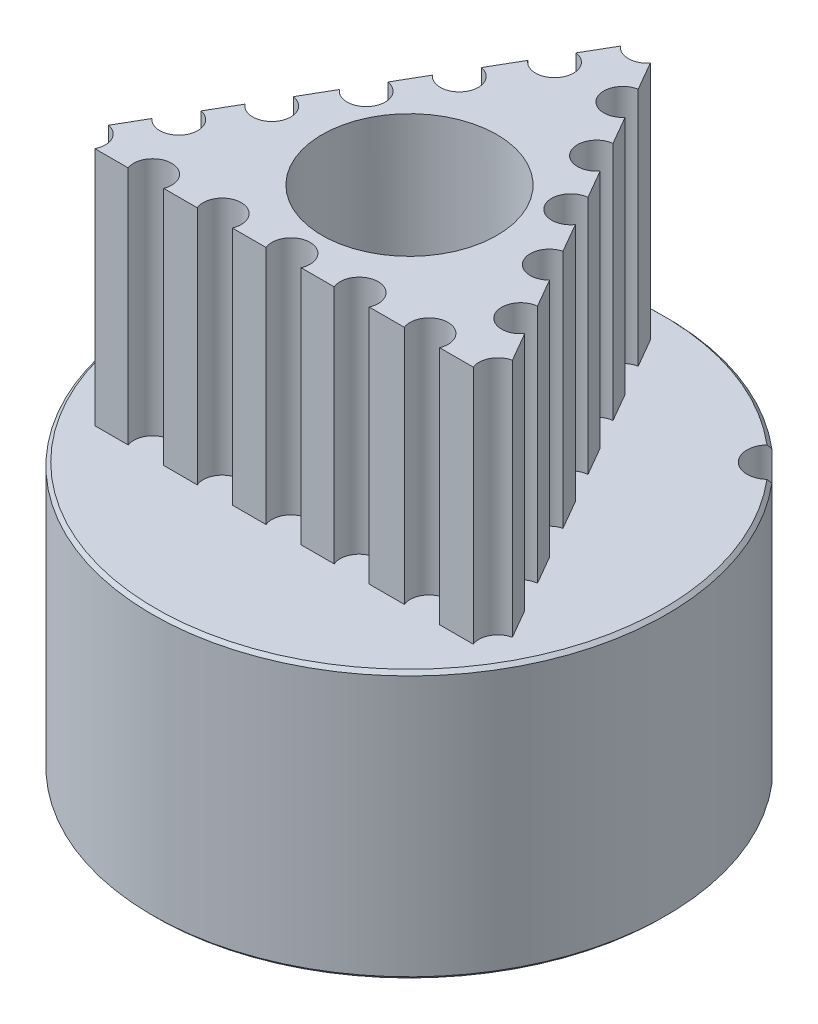
SolidWorks part; units mm, degrees
material "6061 slitina"
ref_plane "Přední rovina" through (0, 0, 0) normal (0, 0, 1) x (1, 0, 0)
ref_plane "Horní rovina" through (0, 0, 0) normal (0, 1, 0) x (1, 0, 0)
ref_plane "Pravá rovina" through (0, 0, 0) normal (1, 0, 0) x (0, 0, -1)
sketch "Skica1" plane through (0, 0, 0) normal (0, 1, 0) x (1, 0, 0)
  circle A0 centre (0, 0) radius 2.5
  arc B0 (-5.7301, 1.0983) -> (-5.3872, 2.2403) centre (-5.6803, 1.7058) ccw
  arc B1 (-5.7301, 1.0983) -> (-5.922, 1.0859) centre (-5.7841, 0.4401) ccw
  arc B2 (-5.922, 1.0859) -> (-6.0197, 1.0387) centre (-5.8743, 0.8624) ccw
  arc B3 (-6.0197, 1.0387) -> (-6.0791, 0.6004) centre (0, 0) ccw
  arc B4 (-6.0791, 0.6004) -> (-5.9974, 0.5289) centre (-5.892, 0.7317) ccw
  arc B5 (-5.9974, 0.5289) -> (-5.8158, 0.466) centre (-5.6927, 1.1148) ccw
  arc B6 (-5.7891, -0.7262) -> (-5.8158, 0.466) centre (-5.9294, -0.133) ccw
  arc B7 (-5.7891, -0.7262) -> (-5.9677, -0.7972) centre (-5.637, -1.3689) ccw
  arc B8 (-5.9677, -0.7972) -> (-6.0461, -0.8723) centre (-5.8532, -0.9951) ccw
  arc B9 (-6.0461, -0.8723) -> (-5.9671, -1.3075) centre (0, 0) ccw
  arc B10 (-5.9671, -1.3075) -> (-5.8673, -1.3503) centre (-5.8297, -1.1248) ccw
  arc B11 (-5.8673, -1.3503) -> (-5.6751, -1.354) centre (-5.7586, -0.6989) ccw
  arc B12 (-5.2813, -2.4796) -> (-5.6751, -1.354) centre (-5.5981, -1.9587) ccw
  arc B13 (-5.2813, -2.4796) -> (-5.4293, -2.6023) centre (-4.9381, -3.0438) ccw
  arc B14 (-5.4293, -2.6023) -> (-5.4806, -2.698) centre (-5.2593, -2.7551) ccw
  arc B15 (-5.4806, -2.698) -> (-5.271, -3.0875) centre (0, 0) ccw
  arc B16 (-5.271, -3.0875) -> (-5.1629, -3.0973) centre (-5.1968, -2.8713) ccw
  arc B17 (-5.1629, -3.0973) -> (-4.979, -3.0415) centre (-5.2608, -2.4442) ccw
  arc B18 (-4.2566, -3.9902) -> (-4.979, -3.0415) centre (-4.7188, -3.5928) ccw
  arc B19 (-4.2566, -3.9902) -> (-4.3594, -4.1527) centre (-3.7559, -4.4208) ccw
  arc B20 (-4.3594, -4.1527) -> (-4.3786, -4.2595) centre (-4.1505, -4.2455) ccw
  arc B21 (-4.3786, -4.2595) -> (-4.059, -4.5652) centre (0, 0) ccw
  arc B22 (-4.059, -4.5652) -> (-3.9531, -4.5412) centre (-4.0552, -4.3366) ccw
  arc B23 (-3.9531, -4.5412) -> (-3.7954, -4.4312) centre (-4.248, -3.9503) ccw
  arc B24 (-2.8152, -5.1103) -> (-3.7954, -4.4312) centre (-3.3776, -4.8751) ccw
  arc B25 (-2.8152, -5.1103) -> (-2.8628, -5.2965) centre (-2.2059, -5.3651) ccw
  arc B26 (-2.8628, -5.2965) -> (-2.8481, -5.4041) centre (-2.6354, -5.3203) ccw
  arc B27 (-2.8481, -5.4041) -> (-2.4496, -5.596) centre (0, 0) ccw
  arc B28 (-2.4496, -5.596) -> (-2.3563, -5.5405) centre (-2.5166, -5.3775) ccw
  arc B29 (-2.3563, -5.5405) -> (-2.2403, -5.3872) centre (-2.8194, -5.0696) ccw
  arc B30 (-1.0983, -5.7301) -> (-2.2403, -5.3872) centre (-1.7058, -5.6803) ccw
  arc B31 (-1.0983, -5.7301) -> (-1.0859, -5.922) centre (-0.4401, -5.7841) ccw
  arc B32 (-1.0859, -5.922) -> (-1.0387, -6.0197) centre (-0.8624, -5.8743) ccw
  arc B33 (-1.0387, -6.0197) -> (-0.6004, -6.0791) centre (0, 0) ccw
  arc B34 (-0.6004, -6.0791) -> (-0.5289, -5.9974) centre (-0.7317, -5.892) ccw
  arc B35 (-0.5289, -5.9974) -> (-0.466, -5.8158) centre (-1.1148, -5.6927) ccw
  arc B36 (0.7262, -5.7891) -> (-0.466, -5.8158) centre (0.133, -5.9294) ccw
  arc B37 (0.7262, -5.7891) -> (0.7972, -5.9677) centre (1.3689, -5.637) ccw
  arc B38 (0.7972, -5.9677) -> (0.8723, -6.0461) centre (0.9951, -5.8532) ccw
  arc B39 (0.8723, -6.0461) -> (1.3075, -5.9671) centre (0, 0) ccw
  arc B40 (1.3075, -5.9671) -> (1.3503, -5.8673) centre (1.1248, -5.8297) ccw
  arc B41 (1.3503, -5.8673) -> (1.354, -5.6751) centre (0.6989, -5.7586) ccw
  arc B42 (2.4796, -5.2813) -> (1.354, -5.6751) centre (1.9587, -5.5981) ccw
  arc B43 (2.4796, -5.2813) -> (2.6023, -5.4293) centre (3.0438, -4.9381) ccw
  arc B44 (2.6023, -5.4293) -> (2.698, -5.4806) centre (2.7551, -5.2593) ccw
  arc B45 (2.698, -5.4806) -> (3.0875, -5.271) centre (0, 0) ccw
  arc B46 (3.0875, -5.271) -> (3.0973, -5.1629) centre (2.8713, -5.1968) ccw
  arc B47 (3.0973, -5.1629) -> (3.0415, -4.979) centre (2.4442, -5.2608) ccw
  arc B48 (3.9902, -4.2566) -> (3.0415, -4.979) centre (3.5928, -4.7188) ccw
  arc B49 (3.9902, -4.2566) -> (4.1527, -4.3594) centre (4.4208, -3.7559) ccw
  arc B50 (4.1527, -4.3594) -> (4.2595, -4.3786) centre (4.2455, -4.1505) ccw
  arc B51 (4.2595, -4.3786) -> (4.5652, -4.059) centre (0, 0) ccw
  arc B52 (4.5652, -4.059) -> (4.5412, -3.9531) centre (4.3366, -4.0552) ccw
  arc B53 (4.5412, -3.9531) -> (4.4312, -3.7954) centre (3.9503, -4.248) ccw
  arc B54 (5.1103, -2.8152) -> (4.4312, -3.7954) centre (4.8751, -3.3776) ccw
  arc B55 (5.1103, -2.8152) -> (5.2965, -2.8628) centre (5.3651, -2.2059) ccw
  arc B56 (5.2965, -2.8628) -> (5.4041, -2.8481) centre (5.3203, -2.6354) ccw
  arc B57 (5.4041, -2.8481) -> (5.596, -2.4496) centre (0, 0) ccw
  arc B58 (5.596, -2.4496) -> (5.5405, -2.3563) centre (5.3775, -2.5166) ccw
  arc B59 (5.5405, -2.3563) -> (5.3872, -2.2403) centre (5.0696, -2.8194) ccw
  arc B60 (5.7301, -1.0983) -> (5.3872, -2.2403) centre (5.6803, -1.7058) ccw
  arc B61 (5.7301, -1.0983) -> (5.922, -1.0859) centre (5.7841, -0.4401) ccw
  arc B62 (5.922, -1.0859) -> (6.0197, -1.0387) centre (5.8743, -0.8624) ccw
  arc B63 (6.0197, -1.0387) -> (6.0791, -0.6004) centre (0, 0) ccw
  arc B64 (6.0791, -0.6004) -> (5.9974, -0.5289) centre (5.892, -0.7317) ccw
  arc B65 (5.9974, -0.5289) -> (5.8158, -0.466) centre (5.6927, -1.1148) ccw
  arc B66 (5.7891, 0.7262) -> (5.8158, -0.466) centre (5.9294, 0.133) ccw
  arc B67 (5.7891, 0.7262) -> (5.9677, 0.7972) centre (5.637, 1.3689) ccw
  arc B68 (5.9677, 0.7972) -> (6.0461, 0.8723) centre (5.8532, 0.9951) ccw
  arc B69 (6.0461, 0.8723) -> (5.9671, 1.3075) centre (0, 0) ccw
  arc B70 (5.9671, 1.3075) -> (5.8673, 1.3503) centre (5.8297, 1.1248) ccw
  arc B71 (5.8673, 1.3503) -> (5.6751, 1.354) centre (5.7586, 0.6989) ccw
  arc B72 (5.2813, 2.4796) -> (5.6751, 1.354) centre (5.5981, 1.9587) ccw
  arc B73 (5.2813, 2.4796) -> (5.4293, 2.6023) centre (4.9381, 3.0438) ccw
  arc B74 (5.4293, 2.6023) -> (5.4806, 2.698) centre (5.2593, 2.7551) ccw
  arc B75 (5.4806, 2.698) -> (5.271, 3.0875) centre (0, 0) ccw
  arc B76 (5.271, 3.0875) -> (5.1629, 3.0973) centre (5.1968, 2.8713) ccw
  arc B77 (5.1629, 3.0973) -> (4.979, 3.0415) centre (5.2608, 2.4442) ccw
  arc B78 (4.2566, 3.9902) -> (4.979, 3.0415) centre (4.7188, 3.5928) ccw
  arc B79 (4.2566, 3.9902) -> (4.3594, 4.1527) centre (3.7559, 4.4208) ccw
  arc B80 (4.3594, 4.1527) -> (4.3786, 4.2595) centre (4.1505, 4.2455) ccw
  arc B81 (4.3786, 4.2595) -> (4.059, 4.5652) centre (0, 0) ccw
  arc B82 (4.059, 4.5652) -> (3.9531, 4.5412) centre (4.0552, 4.3366) ccw
  arc B83 (3.9531, 4.5412) -> (3.7954, 4.4312) centre (4.248, 3.9503) ccw
  arc B84 (2.8152, 5.1103) -> (3.7954, 4.4312) centre (3.3776, 4.8751) ccw
  arc B85 (2.8152, 5.1103) -> (2.8628, 5.2965) centre (2.2059, 5.3651) ccw
  arc B86 (2.8628, 5.2965) -> (2.8481, 5.4041) centre (2.6354, 5.3203) ccw
  arc B87 (2.8481, 5.4041) -> (2.4496, 5.596) centre (0, 0) ccw
  arc B88 (2.4496, 5.596) -> (2.3563, 5.5405) centre (2.5166, 5.3775) ccw
  arc B89 (2.3563, 5.5405) -> (2.2403, 5.3872) centre (2.8194, 5.0696) ccw
  arc B90 (1.0983, 5.7301) -> (2.2403, 5.3872) centre (1.7058, 5.6803) ccw
  arc B91 (1.0983, 5.7301) -> (1.0859, 5.922) centre (0.4401, 5.7841) ccw
  arc B92 (1.0859, 5.922) -> (1.0387, 6.0197) centre (0.8624, 5.8743) ccw
  arc B93 (1.0387, 6.0197) -> (0.6004, 6.0791) centre (0, 0) ccw
  arc B94 (0.6004, 6.0791) -> (0.5289, 5.9974) centre (0.7317, 5.892) ccw
  arc B95 (0.5289, 5.9974) -> (0.466, 5.8158) centre (1.1148, 5.6927) ccw
  arc B96 (-0.7262, 5.7891) -> (0.466, 5.8158) centre (-0.133, 5.9294) ccw
  arc B97 (-0.7262, 5.7891) -> (-0.7972, 5.9677) centre (-1.3689, 5.637) ccw
  arc B98 (-0.7972, 5.9677) -> (-0.8723, 6.0461) centre (-0.9951, 5.8532) ccw
  arc B99 (-0.8723, 6.0461) -> (-1.3075, 5.9671) centre (0, 0) ccw
  arc B100 (-1.3075, 5.9671) -> (-1.3503, 5.8673) centre (-1.1248, 5.8297) ccw
  arc B101 (-1.3503, 5.8673) -> (-1.354, 5.6751) centre (-0.6989, 5.7586) ccw
  arc B102 (-2.4796, 5.2813) -> (-1.354, 5.6751) centre (-1.9587, 5.5981) ccw
  arc B103 (-2.4796, 5.2813) -> (-2.6023, 5.4293) centre (-3.0438, 4.9381) ccw
  arc B104 (-2.6023, 5.4293) -> (-2.698, 5.4806) centre (-2.7551, 5.2593) ccw
  arc B105 (-2.698, 5.4806) -> (-3.0875, 5.271) centre (0, 0) ccw
  arc B106 (-3.0875, 5.271) -> (-3.0973, 5.1629) centre (-2.8713, 5.1968) ccw
  arc B107 (-3.0973, 5.1629) -> (-3.0415, 4.979) centre (-2.4442, 5.2608) ccw
  arc B108 (-3.9902, 4.2566) -> (-3.0415, 4.979) centre (-3.5928, 4.7188) ccw
  arc B109 (-3.9902, 4.2566) -> (-4.1527, 4.3594) centre (-4.4208, 3.7559) ccw
  arc B110 (-4.1527, 4.3594) -> (-4.2595, 4.3786) centre (-4.2455, 4.1505) ccw
  arc B111 (-4.2595, 4.3786) -> (-4.5652, 4.059) centre (0, 0) ccw
  arc B112 (-4.5652, 4.059) -> (-4.5412, 3.9531) centre (-4.3366, 4.0552) ccw
  arc B113 (-4.5412, 3.9531) -> (-4.4312, 3.7954) centre (-3.9503, 4.248) ccw
  arc B114 (-5.1103, 2.8152) -> (-4.4312, 3.7954) centre (-4.8751, 3.3776) ccw
  arc B115 (-5.1103, 2.8152) -> (-5.2965, 2.8628) centre (-5.3651, 2.2059) ccw
  arc B116 (-5.2965, 2.8628) -> (-5.4041, 2.8481) centre (-5.3203, 2.6354) ccw
  arc B117 (-5.4041, 2.8481) -> (-5.596, 2.4496) centre (0, 0) ccw
  arc B118 (-5.596, 2.4496) -> (-5.5405, 2.3563) centre (-5.3775, 2.5166) ccw
  arc B119 (-5.5405, 2.3563) -> (-5.3872, 2.2403) centre (-5.0696, 2.8194) ccw
  dimension "D1" = 5
sketch_block_instance "Blok1-1"
sketch_block "Blok1"
extrude "Přidat vysunutím1" add sketch "Skica1" along normal blind 7 from offset 7.8
sketch "Skica2" plane through (0, 7.8, 0) normal (0, -1, 0) x (1, 0, 0)
  circle A0 centre (0, 0) radius 3.5
  circle A1 centre (0, 0) radius 2.5 construction
  circle A2 centre (0, 0) radius 2.5
  dimension "D1" = 7
extrude "Přidat vysunutím2" add sketch "Skica2" along normal blind 7.8
sketch "Skica3" plane through (0, 14.8, 0) normal (0, 1, 0) x (1, 0, 0)
  circle A0 centre (0, 0) radius 3.5
  circle A1 centre (0, 0) radius 2.5 construction
  circle A2 centre (0, 0) radius 2.5
  dimension "D1" = 7
extrude "Přidat vysunutím3" add sketch "Skica3" along normal blind 1.2
sketch "Skica5" plane through (0, 16, 0) normal (0, 1, 0) x (1, 0, 0)
  circle A0 centre (0, 0) radius 7.5
  circle A3 centre (0, 0) radius 3.5 construction
  circle A4 centre (0, 0) radius 3.5
  dimension "D1" = 15
extrude "Přidat vysunutím4" add sketch "Skica5" against normal up to surface (1.2 mm away) separate body up to face at (0, 14.8, 0)
sketch "Skica6" plane through (0, 0, 0) normal (0, -1, 0) x (1, 0, 0)
  circle A0 centre (0, 0) radius 7.5
  circle A1 centre (0, 0) radius 3.5 construction
  circle A2 centre (0, 0) radius 3.5
  circle A3 centre (0, 0) radius 7.5 construction
extrude "Přidat vysunutím5" add sketch "Skica6" against normal up to surface (7.8 mm away) separate body up to face at (0, 7.8, 0)
chamfer "Zkosení1" distance 0.1 angle 45 2 edges at (0, 14.8, 7.5) (0, 16, 7.5)
chamfer "Zkosení2" distance 0.1 angle 45 2 edges at (0, 0, -2.5) (0, 16, 2.5)
chamfer "Zkosení3" distance 0.1 angle 45 2 edges at (0, 0, -7.5) (0, 7.8, 7.5)
sketch "Sketch8" plane through (0, 16, 0) normal (0, 1, 0) x (1, 0, 0)
  circle A0 centre (0, 0) radius 6.65
extrude "Cut-Extrude2" cut sketch "Sketch8" against normal blind 5 flip side to cut contours A0
ref_plane "Plane1" through (0, 0, -7.5) normal (0, 0, -1) x (-1, 0, 0)
ref_plane "Plane2" through (-7.5, 0, 0) normal (-1, 0, 0) x (0, 0, 1)
sketch "Sketch20" plane through (-7.5, 0, 0) normal (-1, 0, 0) x (0, 0, 1)
  line L0 (0, 0.1) -> (0, 7.7)
  line L1 (-7.5, 0.1) -> (7.5, 0.1) construction
  line L2 (7.5, 7.7) -> (-7.5, 7.7) construction
  circle A0 centre (0, 3.9) radius 1.5
sketch "Sketch25" plane through (0, 7.8, 0) normal (0, 1, 0) x (1, 0, 0)
  line L0 (-0.7179, 6.0965) -> (-0.9071, 5.7689)
  line L5 (-5.5084, -3.67) -> (-4.5368, -3.67)
  line L6 (5.926, -2.9242) -> (5.4338, -2.0716)
  line L9 (-5.4363, -2.0759) -> (-5.8989, -2.8773)
  line L23 (-3.4987, -3.67) -> (-2.5208, -3.67)
  line L24 (-4.4422, -0.3541) -> (-4.912, -1.1678)
  line L26 (-1.4992, -3.67) -> (-0.513, -3.67)
  line L27 (2.4958, -3.67) -> (3.5189, -3.67)
  line L28 (4.926, -1.192) -> (4.4459, -0.3606)
  line L29 (4.549, -3.67) -> (5.5306, -3.67)
  line L30 (0.5086, -3.67) -> (1.4742, -3.67)
  line L31 (3.9112, 0.5657) -> (3.4185, 1.419)
  line L32 (1.9163, 4.0209) -> (1.4364, 4.8521)
  line L33 (-1.4233, 4.8748) -> (-1.9185, 4.0171)
  line L34 (2.9152, 2.2908) -> (2.4274, 3.1357)
  line L35 (0.9141, 5.7568) -> (0.4321, 6.5916)
  line L37 (-2.4409, 3.1122) -> (-2.9162, 2.2891)
  line L39 (-0.7179, 6.0965) -> (-0.4321, 6.5916)
  line L40 (-3.4352, 1.3901) -> (-3.9277, 0.5371)
  line L42 (-0.4321, 6.5916) -> (-0.9071, 5.7689) [skipped]
  arc A24 (-0.4321, 6.5916) -> (0.4321, 6.5916) centre (0, 6.94) ccw
  arc A25 (-1.4233, 4.8748) -> (-0.9071, 5.7689) centre (-0.9887, 5.22) ccw
  arc A26 (-2.4409, 3.1122) -> (-1.9185, 4.0171) centre (-2.0176, 3.471) ccw
  arc A27 (0.9141, 5.7568) -> (1.4364, 4.8521) centre (1.0128, 5.2106) ccw
  arc A28 (1.9163, 4.0209) -> (2.4274, 3.1357) centre (1.9844, 3.4701) ccw
  arc A29 (-3.4352, 1.3901) -> (-2.9162, 2.2891) centre (-3.0054, 1.7413) ccw
  arc A30 (-4.4422, -0.3541) -> (-3.9277, 0.5371) centre (-4.0048, -0.0125) ccw
  arc A31 (-5.4363, -2.0759) -> (-4.912, -1.1678) centre (-5.0165, -1.7129) ccw
  arc A32 (-5.5084, -3.67) -> (-5.8989, -2.8773) centre (-6.0049, -3.4221) ccw
  arc A33 (-3.4987, -3.67) -> (-4.5368, -3.67) centre (-4.0177, -3.4735) ccw
  arc A34 (-1.4992, -3.67) -> (-2.5208, -3.67) centre (-2.01, -3.4529) ccw
  arc A35 (0.5086, -3.67) -> (-0.513, -3.67) centre (-0.0022, -3.4529) ccw
  arc A36 (2.4958, -3.67) -> (1.4742, -3.67) centre (1.985, -3.4529) ccw
  arc A37 (4.549, -3.67) -> (3.5189, -3.67) centre (4.0339, -3.4632) ccw
  arc A38 (2.9152, 2.2908) -> (3.4185, 1.419) centre (2.9643, 1.738) ccw
  arc A39 (3.9112, 0.5657) -> (4.4459, -0.3606) centre (4.05, 0.0283) ccw
  arc A40 (4.926, -1.192) -> (5.4338, -2.0716) centre (4.9859, -1.7438) ccw
  arc A41 (5.926, -2.9242) -> (5.5306, -3.67) centre (6.0467, -3.4659) ccw
  point P0 (-1.0017, 5.205)
  point P6 (-2.0034, 3.47)
  point P7 (-3.0051, 1.735)
  point P9 (-4.0068, 0)
  point P10 (-5.0085, -1.735)
  point P11 (5.0085, -1.735)
  point P12 (4.0068, 0)
  point P13 (3.0051, 1.735)
  point P14 (2.0034, 3.47)
  point P15 (1.0017, 5.205)
  point P16 (-4.0068, -3.47)
  point P20 (-2.0034, -3.47)
  point P21 (0, -3.47)
  point P23 (2.0034, -3.47)
  point P24 (4.0068, -3.47)
sketch "Sketch30" plane through (0, 0, 0) normal (0, -1, 0) x (1, 0, 0)
  line L0 (0, 0) -> (6.782, 0)
  line L1 (6.782, 0) -> (0, -6.782)
  line L2 (-0.1186, 0) -> (3.391, -3.391)
  line L3 (3.391, -3.391) -> (4.7956, -4.7956)
  line L4 (4.7956, -4.7956) -> (5.2326, -5.2326)
  circle A0 centre (0, 0) radius 6.782
  circle A1 centre (0, 0) radius 7.4 construction
  circle A2 centre (5.2326, -5.2326) radius 0.618
sketch "Sketch31" plane through (0, 0, 0) normal (0, -1, 0) x (1, 0, 0)
  circle A1 centre (0, 0) radius 2.55
sketch "Sketch19" plane through (0, 0, -7.5) normal (0, 0, -1) x (-1, 0, 0)
  line L0 (0, 0.1) -> (0, 7.7)
  line L1 (7.5, 0.1) -> (-7.5, 0.1) construction
  line L2 (-7.5, 7.7) -> (7.5, 7.7) construction
  circle A0 centre (0, 3.9) radius 1.5
sketch "Sketch32" plane through (0, 7.8, 0) normal (0, 1, 0) x (1, 0, 0)
  circle A0 centre (0, 0) radius 6.65
extrude "Cut-Extrude3" cut sketch "Sketch32" along normal blind 7
extrude "Boss-Extrude1" add sketch "Sketch25" along normal blind 7
sketch "Sketch34" plane through (0, 16, 0) normal (0, 1, 0) x (1, 0, 0)
  circle A0 centre (0, 0) radius 2.55
extrude "Cut-Extrude4" cut sketch "Sketch34" against normal blind 30
extrude "Cut-Extrude5" cut sketch "Sketch20" against normal blind 8 contours A0
extrude "Cut-Extrude6" cut sketch "Sketch19" against normal blind 8 contours A0
extrude "Cut-Extrude7" cut sketch "Sketch30" against normal blind 8 contours A2
sketch "Sketch36" plane through (0, 14.8, 0) normal (0, -1, 0) x (1, 0, 0)
  circle A0 centre (0, 0) radius 10.4821
extrude "Cut-Extrude8" cut sketch "Sketch36" against normal blind 10
